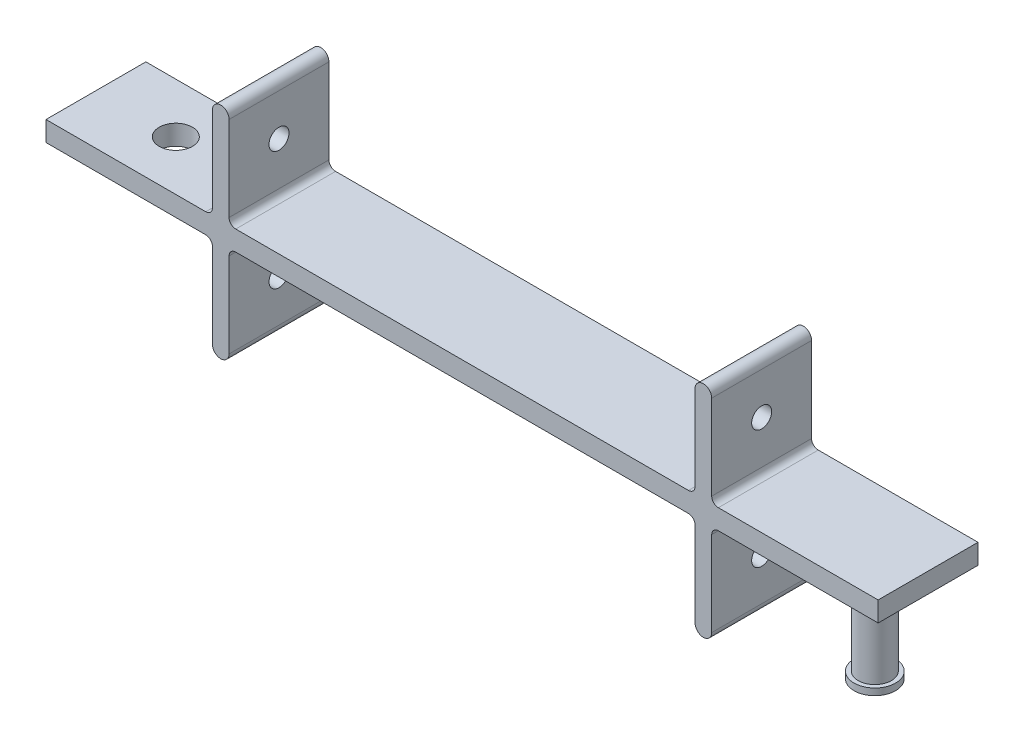
SolidWorks part; units mm, degrees
material "1100-H26 Rod (SS)"
ref_plane "Front Plane" through (0, 0, 0) normal (0, 0, 1) x (1, 0, 0)
ref_plane "Top Plane" through (0, 0, 0) normal (0, 1, 0) x (1, 0, 0)
ref_plane "Right Plane" through (0, 0, 0) normal (1, 0, 0) x (0, 0, -1)
sketch "Sketch1" plane through (0, 0, 0) normal (0, 0, 1) x (1, 0, 0)
  line L0 (-28.8636, 0) -> (-48.8636, 0)
  line L1 (-28.8636, 0) -> (-28.8636, 6)
  line L2 (-28.8636, 6) -> (-48.8636, 6)
  line L3 (-48.8636, 6) -> (-48.8636, 36)
  line L4 (-48.8636, 36) -> (-53.8636, 36)
  line L5 (-53.8636, 36) -> (-53.8636, 6)
  line L6 (-53.8636, 6) -> (-193.8636, 6)
  line L7 (-193.8636, 6) -> (-193.8636, 36)
  line L8 (-193.8636, 36) -> (-198.8636, 36)
  line L9 (-198.8636, 36) -> (-198.8636, 6)
  line L10 (-198.8636, 6) -> (-218.8636, 6)
  line L11 (-218.8636, 6) -> (-218.8636, 0)
  line L12 (-198.8636, 0) -> (-218.8636, 0)
  line L13 (-193.8636, 0) -> (-53.8636, 0)
  line L15 (-48.8636, 0) -> (-48.8636, -30)
  line L16 (-48.8636, -30) -> (-53.8636, -30)
  line L17 (-53.8636, 0) -> (-53.8636, -30)
  line L18 (-193.8636, 0) -> (-193.8636, -30)
  line L19 (-193.8636, -30) -> (-198.8636, -30)
  line L20 (-198.8636, 0) -> (-198.8636, -30)
  dimension "D1" = 140
  dimension "D2" = 150
  dimension "D3" = 30
  dimension "D4" = 20
  dimension "D5" = 6
  dimension "D6" = 5
  dimension "D7" = 30
  dimension "D8" = 30
  dimension "D9" = 5
extrude "Boss-Extrude1" add sketch "Sketch1" along normal blind 30
sketch "Sketch2" plane through (-198.8636, 0, 0) normal (-1, 0, 0) x (0, 0, 1)
  line L0 (15, 6) -> (15, 21) construction
  line L1 (30, 6) -> (0, 6) construction
  circle A0 centre (15, 21) radius 3
  dimension "D2" = 6
  dimension "D1" = 15
fillet "Fillet1" radius 2 2 edges at (-193.8636, 6, 15) (-198.8636, 6, 15)
fillet "Fillet2" 2 edges at (-198.8636, 36, 15) (-193.8636, 36, 15) type full round first side face at (-198.8636, 22, 15) second side face at (-193.8636, 22, 15) middle face at (-196.3636, 36, 15)
fillet "Fillet3" 2 edges at (-53.8636, 36, 15) (-48.8636, 36, 15) type full round first side face at (-53.8636, 21, 15) second side face at (-48.8636, 21, 15) middle face at (-51.3636, 36, 15)
fillet "Fillet4" radius 2 2 edges at (-48.8636, 6, 15) (-53.8636, 6, 15)
extrude "Cut-Extrude4" cut sketch "Sketch2" against normal blind 163 contours A0
sketch "Sketch9" plane through (0, 0, 0) normal (0, 0, -1) x (-1, 0, 0)
  line L1 (218.8636, 6) -> (228.8636, 6)
  line L2 (218.8636, 6) -> (218.8636, 0)
  line L3 (218.8636, 0) -> (228.8636, 0)
  line L4 (228.8636, 6) -> (228.8636, 0)
  dimension "D1" = 10
extrude "Boss-Extrude8" add sketch "Sketch9" against normal blind 30
sketch "Sketch14" plane through (0, 0, 0) normal (0, 0, -1) x (-1, 0, 0)
  line L1 (228.8636, 6) -> (248.8636, 6)
  line L2 (228.8636, 6) -> (228.8636, 0)
  line L3 (228.8636, 0) -> (248.8636, 0)
  line L4 (248.8636, 6) -> (248.8636, 0)
  dimension "D1" = 20
extrude "Boss-Extrude12" add sketch "Sketch14" against normal blind 30
fillet "Fillet10" 2 edges at (-48.8636, -30, 15) (-53.8636, -30, 15) type full round first side face at (-48.8636, -15, 15) second side face at (-53.8636, -15, 15) middle face at (-51.3636, -30, 15)
fillet "Fillet11" 2 edges at (-193.8636, -30, 15) (-198.8636, -30, 15) type full round first side face at (-193.8636, -15, 15) second side face at (-198.8636, -15, 15) middle face at (-196.3636, -30, 15)
fillet "Fillet12" radius 2 4 edges at (-198.8636, 0, 15) (-193.8636, 0, 15) (-53.8636, 0, 15) (-48.8636, 0, 15)
sketch "Sketch16" plane through (-48.8636, 0, 0) normal (1, 0, 0) x (0, 0, -1)
  line L0 (-15, -2) -> (-15, -27.5) construction
  line L1 (0, -2) -> (-30, -2) construction
  line L2 (-30, -27.5) -> (0, -27.5) construction
  circle A0 centre (-15, -14.75) radius 3
  dimension "D1" = 6
extrude "Cut-Extrude6" cut sketch "Sketch16" against normal blind 200
sketch "Sketch17" plane through (0, 0, 0) normal (0, 0, -1) x (-1, 0, 0)
  line L1 (28.8636, 6) -> (-1.1364, 6)
  line L2 (28.8636, 6) -> (28.8636, 0)
  line L3 (28.8636, 0) -> (-1.1364, 0)
  line L4 (-1.1364, 6) -> (-1.1364, 0)
  dimension "D1" = 30
extrude "Boss-Extrude15" add sketch "Sketch17" against normal blind 30
sketch "Sketch20" plane through (0, 0, 0) normal (0, -1, 0) x (-1, 0, 0)
  line L0 (46.8636, -15) -> (14.8636, -15) construction
  line L1 (46.8636, -30) -> (46.8636, 0) construction
  circle A0 centre (14.8636, -15) radius 5
  dimension "D2" = 10
  dimension "D1" = 32
extrude "Boss-Extrude16" add sketch "Sketch20" along normal blind 30
sketch "Sketch21" plane through (0, -30, 0) normal (0, -1, 0) x (1, 0, 0)
  circle A0 centre (-14.8636, 15) radius 6.25
  dimension "D1" = 12.5
extrude "Boss-Extrude17" add sketch "Sketch21" against normal blind 2
sketch "Sketch22" plane through (0, 6, 0) normal (0, 1, 0) x (1, 0, 0)
  line L0 (-200.8636, -15) -> (-248.8636, -15) construction
  line L1 (-200.8636, -30) -> (-200.8636, 0) construction
  line L2 (-248.8636, -30) -> (-248.8636, 0) construction
  circle A0 centre (-224.8636, -15) radius 5
  dimension "D1" = 10
extrude "Cut-Extrude7" cut sketch "Sketch22" against normal blind 10
